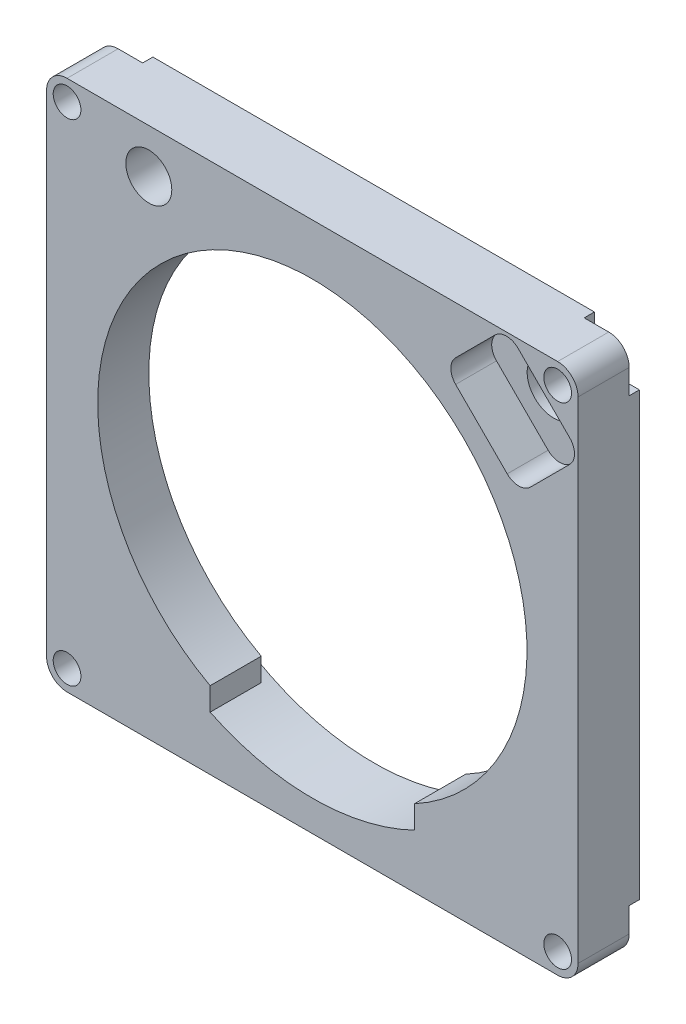
SolidWorks part; units mm, degrees
material "PET"
ref_plane "Front Plane" through (0, 0, 0) normal (0, 0, 1) x (1, 0, 0)
ref_plane "Top Plane" through (0, 0, 0) normal (0, 1, 0) x (1, 0, 0)
ref_plane "Right Plane" through (0, 0, 0) normal (1, 0, 0) x (0, 0, -1)
sketch "Sketch1" plane through (0, 0, 0) normal (0, 0, 1) x (1, 0, 0)
  line L4 (-38.1, -41.275) -> (38.1, -41.275)
  line L5 (41.275, -38.1) -> (41.275, 38.1)
  line L6 (38.1, 41.275) -> (-38.1, 41.275)
  line L7 (-41.275, 38.1) -> (-41.275, -38.1)
  line L8 (-38.1, -41.275) -> (38.1, -41.275)
  line L9 (41.275, -38.1) -> (41.275, 38.1)
  line L10 (38.1, 41.275) -> (-38.1, 41.275)
  line L11 (-41.275, 38.1) -> (-41.275, -38.1)
  line L388 (15.875, -29.3151) -> (15.875, -32.8808) construction
  line L389 (-15.875, -32.8808) -> (-15.875, -29.3151) construction
  line L390 (15.875, -29.3151) -> (15.875, -32.8808)
  line L391 (-15.875, -32.8808) -> (-15.875, -29.3151)
  arc A4 (-41.275, -38.1) -> (-38.1, -41.275) centre (-38.1, -38.1) ccw
  arc A5 (38.1, -41.275) -> (41.275, -38.1) centre (38.1, -38.1) ccw
  arc A6 (41.275, 38.1) -> (38.1, 41.275) centre (38.1, 38.1) ccw
  arc A7 (-38.1, 41.275) -> (-41.275, 38.1) centre (-38.1, 38.1) ccw
  arc A8 (-41.275, -38.1) -> (-38.1, -41.275) centre (-38.1, -38.1) ccw
  arc A9 (38.1, -41.275) -> (41.275, -38.1) centre (38.1, -38.1) ccw
  arc A10 (41.275, 38.1) -> (38.1, 41.275) centre (38.1, 38.1) ccw
  arc A11 (-38.1, 41.275) -> (-41.275, 38.1) centre (-38.1, 38.1) ccw
  arc A388 (15.875, -29.3151) -> (-15.875, -29.3151) centre (0, 0) ccw construction
  arc A389 (-15.875, -32.8808) -> (15.875, -32.8808) centre (0, 0) ccw construction
  arc A390 (15.875, -29.3151) -> (-15.875, -29.3151) centre (0, 0) ccw
  arc A391 (-15.875, -32.8808) -> (15.875, -32.8808) centre (0, 0) ccw
  dimension "D1" = 0
extrude "Boss-Extrude1" add sketch "Sketch1" against normal up to surface (7.9375 mm away)
sketch "Sketch2" plane through (0, 0, -7.9375) normal (0, 0, -1) x (-1, 0, 0)
  line L12 (-34.29, -38.1) -> (-34.29, -41.275)
  line L13 (-34.29, -41.275) -> (34.29, -41.275)
  line L14 (34.29, -41.275) -> (34.29, -38.1)
  line L15 (38.1, -34.29) -> (41.275, -34.29)
  line L16 (41.275, -34.29) -> (41.275, 34.29)
  line L17 (41.275, 34.29) -> (38.1, 34.29)
  line L18 (34.29, 38.1) -> (34.29, 41.275)
  line L19 (34.29, 41.275) -> (-34.29, 41.275)
  line L20 (-34.29, 41.275) -> (-34.29, 38.1)
  line L21 (-38.1, 34.29) -> (-41.275, 34.29)
  line L22 (-41.275, 34.29) -> (-41.275, -34.29)
  line L23 (-41.275, -34.29) -> (-38.1, -34.29)
  line L24 (-34.29, -38.1) -> (-34.29, -41.275)
  line L25 (-34.29, -41.275) -> (34.29, -41.275)
  line L26 (34.29, -41.275) -> (34.29, -38.1)
  line L27 (38.1, -34.29) -> (41.275, -34.29)
  line L28 (41.275, -34.29) -> (41.275, 34.29)
  line L29 (41.275, 34.29) -> (38.1, 34.29)
  line L30 (34.29, 38.1) -> (34.29, 41.275)
  line L31 (34.29, 41.275) -> (-34.29, 41.275)
  line L32 (-34.29, 41.275) -> (-34.29, 38.1)
  line L33 (-38.1, 34.29) -> (-41.275, 34.29)
  line L34 (-41.275, 34.29) -> (-41.275, -34.29)
  line L35 (-41.275, -34.29) -> (-38.1, -34.29)
  circle A0 centre (0, 0) radius 36.5125 construction
  circle A1 centre (0, 0) radius 36.5125
  arc A4 (-34.29, -38.1) -> (-38.1, -34.29) centre (-38.1, -38.1) ccw
  arc A5 (38.1, -34.29) -> (34.29, -38.1) centre (38.1, -38.1) ccw
  arc A6 (34.29, 38.1) -> (38.1, 34.29) centre (38.1, 38.1) ccw
  arc A7 (-38.1, 34.29) -> (-34.29, 38.1) centre (-38.1, 38.1) ccw
  arc A8 (-34.29, -38.1) -> (-38.1, -34.29) centre (-38.1, -38.1) ccw
  arc A9 (38.1, -34.29) -> (34.29, -38.1) centre (38.1, -38.1) ccw
  arc A10 (34.29, 38.1) -> (38.1, 34.29) centre (38.1, 38.1) ccw
  arc A11 (-38.1, 34.29) -> (-34.29, 38.1) centre (-38.1, 38.1) ccw
  dimension "D1" = 0
extrude "Boss-Extrude2" add sketch "Sketch2" along normal blind 1.5875
hole_wizard "#6 Clearance Hole1" positions "Sketch4" profile "Sketch3" hole size "#6" standard "ANSI Inch" end condition through all
sketch "Sketch4" plane through (0, 0, -7.9375) normal (0, 0, -1) x (-1, 0, 0)
  point P0 (-38.1, 38.1)
  point P3 (38.1, 38.1)
  point P6 (38.1, -38.1)
  point P9 (-38.1, -38.1)
sketch "Sketch3" plane through (38.1, 38.1, -7.9375) normal (1, 0, 0) x (0, 1, 0)
  line L0 (0, 0) -> (0, 7.9375)
  line L1 (0, 7.9375) -> (2.1526, 7.9375)
  line L2 (2.1526, 7.9375) -> (2.1526, 0)
  line L5 (2.1526, 0) -> (0, 0)
  line L11 (0, -6.35) -> (0, 107.95) construction
  dimension "Thru Hole Dia." = 4.3053
  dimension "Thru Hole Depth" = 7.9375
sketch "Sketch5" plane through (0, 0, 0) normal (0, 0, 1) x (1, 0, 0)
  circle A0 centre (-25.4, 34.417) radius 3.5712
  dimension "D1" = 7.1425
extrude "Cut-Extrude1" cut sketch "Sketch5" against normal offset from surface (7.9375 mm away) 1.5875 up to face at (0, 0, -9.525)
sketch "Sketch6" plane through (0, 0, -7.9375) normal (0, 0, 1) x (1, 0, 0)
  circle A0 centre (-25.4, 34.417) radius 2.1
  dimension "D1" = 4.2
extrude "Cut-Extrude2" cut sketch "Sketch6" against normal up to next
sketch "Sketch7" plane through (0, 0, 0) normal (0, 0, 1) x (1, 0, 0)
  line L0 (22.255, 30.2707) -> (30.2707, 22.255)
  line L1 (22.255, 33.8628) -> (28.3672, 39.975)
  line L2 (33.8628, 22.255) -> (39.975, 28.3672)
  line L3 (31.9593, 39.975) -> (39.975, 31.9593)
  line L4 (20.4589, 32.0668) -> (41.7711, 30.1632) construction
  line L5 (32.0668, 20.4589) -> (30.1632, 41.7711) construction
  line L6 (24.0439, 34.9334) -> (23.7611, 34.6505) construction
  line L7 (25.246, 28.3573) -> (24.5389, 29.0644) construction
  arc A0 (28.3672, 39.975) -> (31.9593, 39.975) centre (30.1632, 38.179) cw
  arc A1 (39.975, 28.3672) -> (39.975, 31.9593) centre (38.179, 30.1632) ccw
  arc A2 (30.2707, 22.255) -> (33.8628, 22.255) centre (32.0668, 24.051) ccw
  arc A3 (22.255, 33.8628) -> (22.255, 30.2707) centre (24.051, 32.0668) ccw
  point P1 (31.115, 31.115)
  dimension "D3" = 2.54
  dimension "D1" = 0.508
  dimension "D2" = 0.762
extrude "Cut-Extrude3" cut sketch "Sketch7" against normal offset from surface (6.35 mm away) 3.175 up to face at (-27.5, 34.417, -9.525)
hole_wizard "5/16 Clearance Hole1" positions "Sketch9" profile "Sketch8" hole size "5/16" standard "ANSI Inch" end condition through all
sketch "Sketch9" plane through (0, 0, -9.525) normal (0, 0, -1) x (-1, 0, 0)
  point P0 (-31.115, 31.115)
sketch "Sketch8" plane through (31.115, 31.115, -9.525) normal (1, 0, 0) x (0, 1, 0)
  line L0 (0, 0) -> (0, 9.525)
  line L1 (0, 9.525) -> (4.1021, 9.525)
  line L2 (4.1021, 9.525) -> (4.1021, 0)
  line L5 (4.1021, 0) -> (0, 0)
  line L11 (0, -6.35) -> (0, 107.95) construction
  dimension "Thru Hole Dia." = 8.2042
  dimension "Thru Hole Depth" = 9.525
